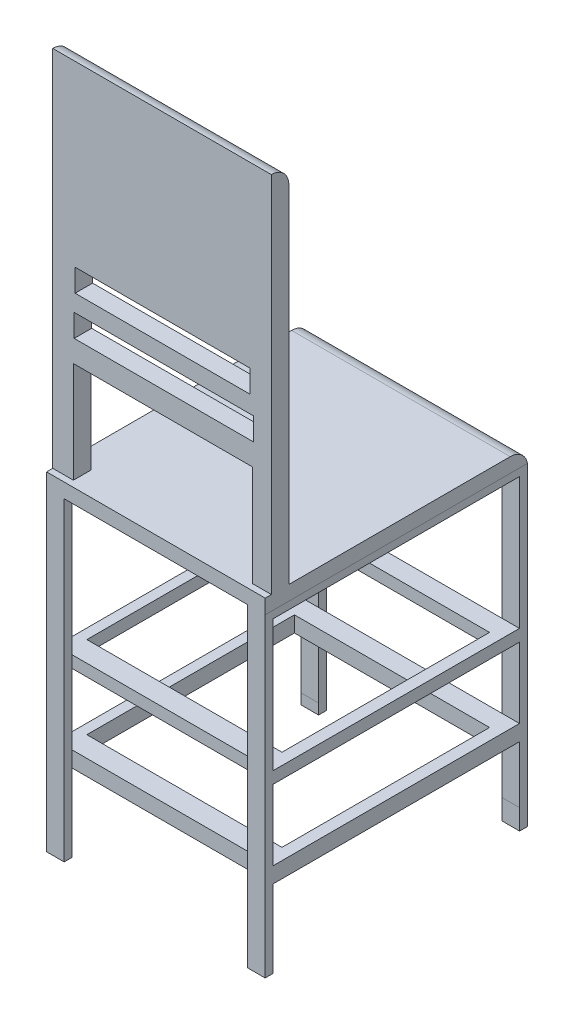
SolidWorks part; units mm, degrees
ref_plane "Front Plane" through (0, 0, 0) normal (0, 0, 1) x (1, 0, 0)
ref_plane "Top Plane" through (0, 0, 0) normal (0, 1, 0) x (1, 0, 0)
ref_plane "Right Plane" through (0, 0, 0) normal (1, 0, 0) x (0, 0, -1)
sketch "Sketch1" plane through (0, 0, 0) normal (0, 1, 0) x (1, 0, 0)
  line L0 (-281.7809, 346.6236) -> (-256.3809, 346.6236)
  line L5 (10.3415, 346.6236) -> (35.7415, 346.6236)
  line L6 (10.3415, 346.6236) -> (10.3415, -34.3764)
  line L7 (10.3415, -34.3764) -> (35.7415, -34.3764)
  line L8 (35.7415, 346.6236) -> (35.7415, -34.3764)
  line L9 (-256.3809, 346.6236) -> (-256.3809, -34.3764)
  line L10 (-256.3809, -34.3764) -> (-281.7809, -34.3764)
  line L11 (-281.7809, -34.3764) -> (-281.7809, 346.6236)
  dimension "D1" = 25.4
  dimension "D2" = 381
  dimension "D3" = 25.4
  dimension "D4" = 25.4
extrude "Boss-Extrude1" add sketch "Sketch1" along normal blind 457.2
sketch "Sketch5" plane through (35.7415, 0, 0) normal (1, 0, 0) x (0, 0, -1)
  line L1 (-23.041, 446.3392) -> (335.2882, 446.3392)
  line L2 (-23.041, 446.3392) -> (-23.041, 15.324)
  line L3 (-23.041, 15.324) -> (335.2882, 15.324)
  line L4 (335.2882, 446.3392) -> (335.2882, 15.324)
extrude "Cut-Extrude1" cut sketch "Sketch5" against normal blind 457.2
sketch "Sketch13" plane through (0, 0, 0) normal (1, 0, 0) x (0, 0, -1)
  line L1 (-34.3764, 457.2) -> (346.7649, 457.2)
  line L2 (-34.3764, 457.2) -> (-34.3764, 478.219)
  line L3 (-34.3764, 478.219) -> (346.7649, 478.219)
  line L4 (346.7649, 457.2) -> (346.7649, 478.219)
extrude "Boss-Extrude7" add sketch "Sketch13" against normal blind 281.94 and the other way blind 35.814
sketch "Sketch14" plane through (0, 0, 0) normal (0, 0, 1) x (1, 0, 0)
  line L0 (-281.94, 478.219) -> (-281.94, 457.2) construction
  line L1 (-281.94, 467.7095) -> (35.814, 467.7095)
  line L2 (-281.94, 467.7095) -> (-281.94, 993.7957)
  line L3 (-281.94, 993.7957) -> (35.814, 993.7957)
  line L4 (35.814, 467.7095) -> (35.814, 993.7957)
extrude "Boss-Extrude8" add sketch "Sketch14" along normal blind 25.4
sketch "Sketch17" plane through (0, 0, 25.4) normal (0, 0, 1) x (1, 0, 0)
  line L0 (-281.94, 478.219) -> (35.814, 478.219) construction
  line L1 (-251.9532, 625.095) -> (8.599, 625.095)
  line L2 (-251.9532, 625.095) -> (-251.9532, 478.219)
  line L3 (-251.9532, 478.219) -> (8.599, 478.219)
  line L4 (8.599, 625.095) -> (8.599, 478.219)
  line L6 (-251.9532, 677.7598) -> (8.599, 677.7598)
  line L7 (-251.9532, 677.7598) -> (-251.9532, 648.6556)
  line L8 (-251.9532, 648.6556) -> (8.599, 648.6556)
  line L9 (8.599, 677.7598) -> (8.599, 648.6556)
  line L10 (-251.9532, 724.881) -> (8.599, 724.881)
  line L11 (-251.9532, 724.881) -> (-251.9532, 695.7767)
  line L12 (-251.9532, 695.7767) -> (8.599, 695.7767)
  line L13 (8.599, 724.881) -> (8.599, 695.7767)
extrude "Cut-Extrude3" cut sketch "Sketch17" against normal blind 25.4
sketch "Sketch18" plane through (0, 0, 0) normal (0, 0, 1) x (1, 0, 0)
  line L0 (-281.94, 993.7957) -> (-281.94, 1247.7957)
  line L1 (35.814, 993.7957) -> (35.814, 1247.7957)
  line L2 (35.814, 1247.7957) -> (-281.94, 1247.7957)
  line L12 (-281.94, 478.219) -> (-251.9532, 478.219)
  line L13 (-251.9532, 478.219) -> (-251.9532, 625.095)
  line L14 (-251.9532, 625.095) -> (8.599, 625.095)
  line L15 (8.599, 625.095) -> (8.599, 478.219)
  line L16 (8.599, 478.219) -> (35.814, 478.219)
  line L17 (35.814, 478.219) -> (35.814, 993.7957)
  line L18 (35.814, 993.7957) -> (-281.94, 993.7957)
  line L19 (-281.94, 993.7957) -> (-281.94, 478.219)
  line L20 (-281.94, 478.219) -> (-251.9532, 478.219)
  line L21 (-251.9532, 478.219) -> (-251.9532, 625.095)
  line L22 (-251.9532, 625.095) -> (8.599, 625.095)
  line L23 (8.599, 625.095) -> (8.599, 478.219)
  line L24 (8.599, 478.219) -> (35.814, 478.219)
  line L25 (35.814, 478.219) -> (35.814, 993.7957)
  line L27 (-281.94, 993.7957) -> (-281.94, 478.219)
  dimension "D1" = 254
  dimension "D2" = 0
extrude "Boss-Extrude9" add sketch "Sketch18" along normal blind 25.4
sketch "Sketch19" plane through (0, 0, 0) normal (0, 0, 1) x (1, 0, 0)
  line L1 (-250.7869, 690.0925) -> (10.1853, 690.0925)
  line L2 (-250.7869, 690.0925) -> (-250.7869, 657.3037)
  line L3 (-250.7869, 657.3037) -> (10.1853, 657.3037)
  line L4 (10.1853, 690.0925) -> (10.1853, 657.3037)
  line L5 (-249.4486, 747.6402) -> (4.5514, 747.6402)
  line L6 (-249.4486, 747.6402) -> (-249.4486, 714.8514)
  line L7 (-249.4486, 714.8514) -> (4.5514, 714.8514)
  line L8 (4.5514, 747.6402) -> (4.5514, 714.8514)
  dimension "D1" = 254
  dimension "D2" = 260.9722
extrude "Cut-Extrude6" cut sketch "Sketch19" along normal blind 35.56
fillet "Fillet1" radius 25.4 1 edges at (-123.063, 1247.7957, 0)
fillet "Fillet2" radius 25.4 1 edges at (-123.063, 478.219, -346.7649)
sketch "Sketch20" plane through (0, 0, 0) normal (1, 0, 0) x (0, 0, -1)
  line L0 (174.7647, 0) -> (-174.7647, 0) construction
  line L1 (335.4282, 0) -> (-23.041, 0)
  line L2 (335.4282, 0) -> (335.4282, 15.324)
  line L3 (335.4282, 15.324) -> (-23.041, 15.324)
  line L4 (-23.041, 0) -> (-23.041, 15.324)
extrude "Cut-Extrude7" cut sketch "Sketch20" against normal blind 288.544
sketch "Sketch21" plane through (0, 0, 0) normal (1, 0, 0) x (0, 0, -1)
  line L0 (-23.041, 446.3392) -> (-23.041, 15.324) construction
  line L1 (174.7647, 0) -> (-174.7647, 0) construction
  line L2 (-23.041, 29.6414) -> (335.4282, 29.6414)
  line L3 (-23.041, 29.6414) -> (-23.041, 0)
  line L4 (-23.041, 0) -> (335.4282, 0)
  line L5 (335.4282, 29.6414) -> (335.4282, 0)
extrude "Cut-Extrude8" cut sketch "Sketch21" along normal blind 80.772
sketch "Sketch22" plane through (0, 0, 0) normal (1, 0, 0) x (0, 0, -1)
  line L0 (-23.041, 446.3392) -> (-23.041, 0) construction
  line L1 (-23.041, 255.2262) -> (335.2882, 255.2262)
  line L2 (-23.041, 255.2262) -> (-23.041, 237.9903)
  line L3 (-23.041, 237.9903) -> (335.2882, 237.9903)
  line L4 (335.2882, 255.2262) -> (335.2882, 237.9903)
  line L5 (335.2882, 29.6414) -> (335.2882, 446.3392) construction
  line L7 (-23.041, 135.506) -> (335.2882, 135.506)
  line L8 (-23.041, 135.506) -> (-23.041, 112.646)
  line L9 (-23.041, 112.646) -> (335.2882, 112.646)
  line L10 (335.2882, 135.506) -> (335.2882, 112.646)
  dimension "D1" = 22.86
extrude "Boss-Extrude10" add sketch "Sketch22" against normal blind 279.146 and the other way up to vertex (35.7415 mm away) other way up to point (35.7415, 457.2, -346.6236)
sketch "Sketch23" plane through (0, 0, 0) normal (0, 1, 0) x (1, 0, 0)
  line L1 (-264.5556, 308.5035) -> (19.0143, 308.5035)
  line L2 (-264.5556, 308.5035) -> (-264.5556, 6.8084)
  line L3 (-264.5556, 6.8084) -> (19.0143, 6.8084)
  line L4 (19.0143, 308.5035) -> (19.0143, 6.8084)
extrude "Cut-Extrude9" cut sketch "Sketch23" against normal blind 279.146 and the other way blind 378.46
sketch "Sketch24" plane through (0, 0, 25.4) normal (0, 0, 1) x (1, 0, 0)
  line L1 (-319.5909, 1415.5521) -> (92.1627, 1415.5521)
  line L2 (-319.5909, 1415.5521) -> (-319.5909, 1006.7822)
  line L3 (-319.5909, 1006.7822) -> (92.1627, 1006.7822)
  line L4 (92.1627, 1415.5521) -> (92.1627, 1006.7822)
extrude "Cut-Extrude11" cut sketch "Sketch24" against normal blind 75.946
fillet "Fillet3" radius 25.4 1 edges at (-123.063, 1006.7822, 0)
